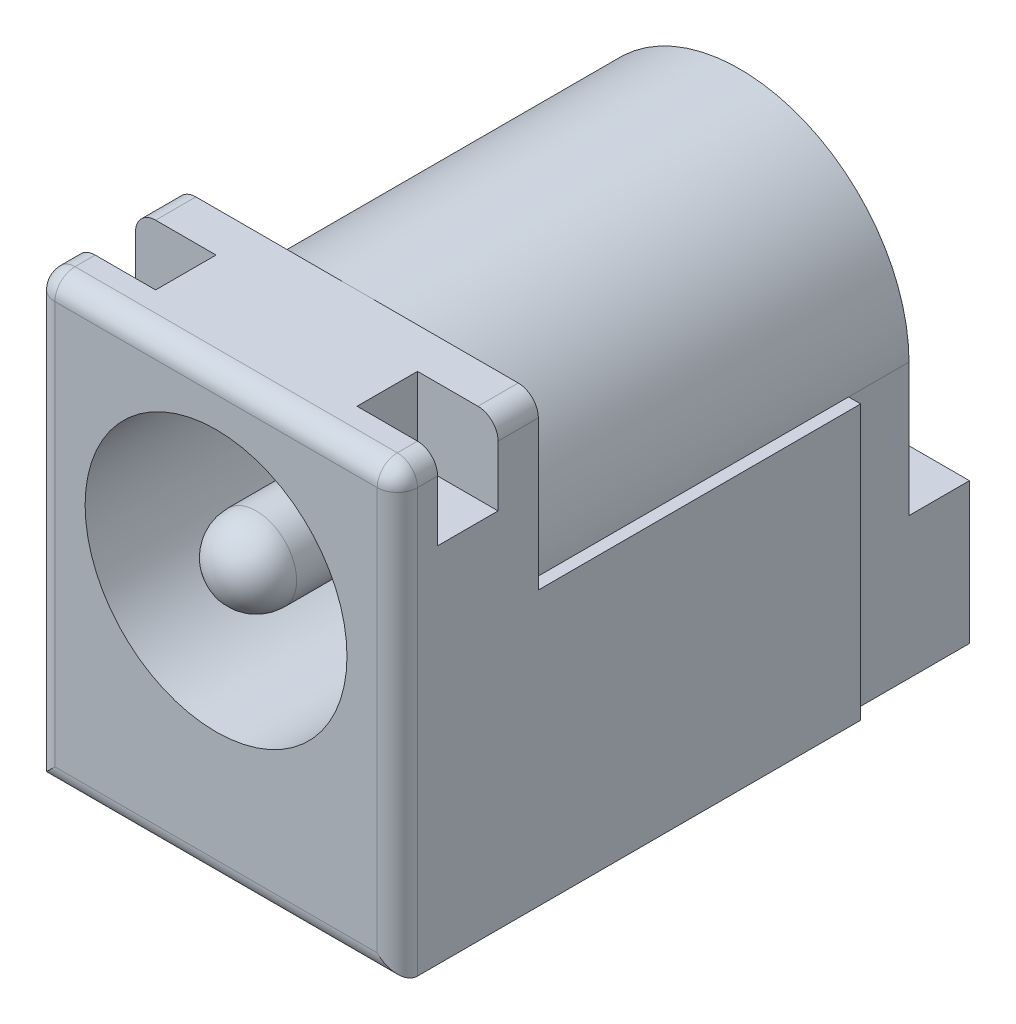
SolidWorks part; units mm, degrees
ref_plane "Front Plane" through (0, 0, 0) normal (0, 0, 1) x (1, 0, 0)
ref_plane "Top Plane" through (0, 0, 0) normal (0, 1, 0) x (1, 0, 0)
ref_plane "Right Plane" through (0, 0, 0) normal (1, 0, 0) x (0, 0, -1)
sketch "Sketch1" plane through (0, 0, 0) normal (0, 0, 1) x (1, 0, 0)
  line L1 (-4.5, 5.5) -> (4.5, 5.5)
  line L2 (-4.5, 5.5) -> (-4.5, -5.5)
  line L3 (-4.5, -5.5) -> (4.5, -5.5)
  line L4 (4.5, 5.5) -> (4.5, -5.5)
  line L5 (-4.5, 5.5) -> (4.5, -5.5) construction
  line L6 (-4.5, -5.5) -> (4.5, 5.5) construction
  point P0 (0, 0)
  dimension "D1" = 9
  dimension "D2" = 11
extrude "Boss-Extrude1" add sketch "Sketch1" against normal blind 14.5
sketch "Sketch2" plane through (0, 0, -14.5) normal (0, 0, -1) x (-1, 0, 0)
  line L0 (-4.2, 1.3) -> (4.2, 1.3)
  line L4 (4.5, 5.5) -> (4.5, -5.5) construction
  line L5 (-4.5, 5.5) -> (4.5, 5.5) construction
  line L6 (-4.2, 1.3) -> (-4.5, 1.3)
  line L7 (-4.5, -5.5) -> (-4.5, 5.5) construction
  line L8 (4.2, 1.3) -> (4.5, 1.3)
  arc A0 (-4.2, 1.3) -> (4.2, 1.3) centre (0, 1.3) cw
  line M3 (-4.5, 5.5) -> (-4.5, -5.5)
  line M5 (4.5, -5.5) -> (4.5, 5.5)
  line M6 (4.5, 5.5) -> (-4.5, 5.5)
  dimension "D2" = 0.3
extrude "Cut-Extrude3" cut sketch "Sketch2" against normal blind 11 contours L6 A0 M6 M3 | A0 L8 M6 M5
sketch "Sketch3" plane through (4.5, 0, 0) normal (1, 0, 0) x (0, 0, -1)
  line L0 (14.5, -5.5) -> (14.5, 1.3)
  line L1 (14.5, -5.5) -> (14.5, 1.3) construction
  line L4 (3.5, 1.3) -> (14.5, 1.3) construction
  line L5 (14.5, 1.3) -> (11.5, 1.3)
  line L6 (11.5, 1.3) -> (11.5, -5.5)
  line L7 (14.5, -5.5) -> (0, -5.5) construction
  line L8 (11.5, -5.5) -> (14.5, -5.5)
  dimension "D1" = 3
extrude "Cut-Extrude4" cut sketch "Sketch3" against normal blind 0.3
mirror "Mirror1" about plane through (0, 0, 0) normal (1, 0, 0) of "Cut-Extrude4"
sketch "Sketch5" plane through (4.2, 0, 0) normal (1, 0, 0) x (0, 0, -1)
  line L0 (14.5, -5.5) -> (14.5, 1.3) construction
  line L1 (14.5, -2) -> (13, -2)
  line L2 (14.5, -2) -> (14.5, 5.5)
  line L3 (14.5, 5.5) -> (13, 5.5)
  line L4 (13, -2) -> (13, 5.5)
  line L5 (14.5, 5.5) -> (3.5, 5.5) construction
  line L6 (11.5, 1.3) -> (11.5, -5.5) construction
  line L7 (11.5, -5.5) -> (14.5, -5.5) construction
  dimension "D1" = 1.5
  dimension "D2" = 3.5
extrude "Cut-Extrude5" cut sketch "Sketch5" against normal through all
sketch "Sketch6" plane through (0, 0, -14.5) normal (0, 0, -1) x (-1, 0, 0)
  line L0 (4.2, -5.5) -> (-4.2, -5.5) construction
  line L1 (-1.75, -5.5) -> (1.75, -5.5)
  line L2 (-1.75, -5.5) -> (-1.75, -2)
  line L3 (-1.75, -2) -> (1.75, -2)
  line L4 (1.75, -5.5) -> (1.75, -2)
  line L5 (4.2, -2) -> (-4.2, -2) construction
  point P8 (0, -5.5)
  point P9 (0, -2)
  dimension "D1" = 3.5
extrude "Cut-Extrude6" cut sketch "Sketch6" against normal up to surface (1.5 mm away) up to face at (0, 0.7, -13)
sketch "Sketch7" plane through (0, 0, -13) normal (0, 0, -1) x (-1, 0, 0)
  line L0 (0, 1.3) -> (0, -7.5) construction
  line L1 (1.5, 1.3) -> (1.5, -7.5)
  line L2 (-1.5, 1.3) -> (-1.5, -7.5)
  line L4 (-4.5891, -9) -> (7.0324, -9) construction
  line L5 (4.2, -5.5) -> (1.75, -5.5) construction
  line L6 (-1.5, 1.3) -> (1.5, 1.3) construction
  line L7 (4.2, 1.3) -> (4.5, 1.3) construction
  arc A0 (1.5, 1.3) -> (-1.5, 1.3) centre (0, 1.3) ccw
  arc A1 (-1.5, -7.5) -> (1.5, -7.5) centre (0, -7.5) ccw
  point P2 (0, -3.1)
  dimension "D2" = 3.5
  dimension "D1" = 3
extrude "Boss-Extrude2" add sketch "Sketch7" along normal blind 0.5
sketch "Sketch8" plane through (0, 0, -13.5) normal (0, 0, -1) x (-1, 0, 0)
  circle A0 centre (0, 1.3) radius 1.375
  circle A2 centre (0, 1.3) radius 1
  dimension "D1" = 2.75
  dimension "D2" = 2
extrude "Boss-Extrude3" add sketch "Sketch8" along normal blind 0.5 contours A0 A2
chamfer "Chamfer1" distance 0.5 angle 45 1 edges at (-1.375, 1.3, -14)
sketch "Sketch9" plane through (0, -5.5, 0) normal (0, -1, 0) x (1, 0, 0)
  line L0 (0, 0) -> (0, -13) construction
  line L1 (-1.25, -7) -> (1.25, -7)
  line L2 (-1.25, -7) -> (-1.25, -7.5)
  line L3 (-1.25, -7.5) -> (1.25, -7.5)
  line L4 (1.25, -7) -> (1.25, -7.5)
  line L5 (1.5, -13) -> (-1.5, -13) construction
  line L6 (-1.25, -7.5) -> (1.25, -7) construction
  point P9 (0, -7.25)
  point P10 (0, -7)
  dimension "D1" = 0.5
  dimension "D2" = 2.5
  dimension "D3" = 5.75
extrude "Boss-Extrude4" add sketch "Sketch9" along normal blind 6
sketch "Sketch10" plane through (0, 0, -7) normal (0, 0, 1) x (1, 0, 0)
  line L0 (-1.25, -11.5) -> (-1.25, -5.5) construction
  line L1 (1.25, -11.5) -> (1.25, -5.5) construction
  line L2 (-1.0662, -9) -> (1.0355, -9) construction
  line L3 (-4.5, -5.5) -> (4.5, -5.5) construction
  line L4 (-1.25, -8.3292) -> (1.25, -8.3292)
  arc A1 (-1.25, -8.3292) -> (1.25, -8.3292) centre (0, -7.5) ccw
  dimension "D1" = 1.5
  dimension "D2" = 3.5
extrude "Cut-Extrude8" cut sketch "Sketch10" against normal blind 0.5
sketch "Sketch11" plane through (0, 0, -13.5) normal (0, 0, -1) x (-1, 0, 0)
  circle A0 centre (0, -7.5) radius 0.6
  dimension "D1" = 1.2
extrude "Cut-Extrude9" cut sketch "Sketch11" against normal through all
sketch "Sketch12" plane through (4.5, 0, 0) normal (1, 0, 0) x (0, 0, -1)
  line L0 (3.5, 5.5) -> (0, 5.5) construction
  line L1 (1, 5.5) -> (2.5, 5.5)
  line L2 (1, 5.5) -> (1, 3.5)
  line L3 (1, 3.5) -> (2.5, 3.5)
  line L4 (2.5, 5.5) -> (2.5, 3.5)
  line L5 (1, 4.7806) -> (0, 4.7806) construction
  line L6 (0, -5.5) -> (0, 5.5) construction
  line L7 (2.5, 4.7806) -> (3.5, 4.7806) construction
  line L8 (3.5, 5.5) -> (3.5, 1.3) construction
  dimension "D1" = 1.5
  dimension "D2" = 2
extrude "Cut-Extrude10" cut sketch "Sketch12" against normal blind 2
mirror "Mirror2" about plane through (0, 0, 0) normal (1, 0, 0) of "Cut-Extrude10"
sketch "Sketch13" plane through (0, 0, 0) normal (0, 0, 1) x (1, 0, 0)
  line L0 (-4.5, -5.5) -> (4.5, -5.5) construction
  circle A0 centre (0, 1) radius 3.25
  circle A1 centre (0, 1) radius 1
  dimension "D1" = 6.5
  dimension "D2" = 6.5
  dimension "D3" = 2
extrude "Cut-Extrude11" cut sketch "Sketch13" against normal blind 12 contours A0 A1
fillet "Fillet1" radius 1 1 edges at (1, 1, 0)
fillet "Fillet2" radius 0.5 8 edges at (-4.5, 5.5, -0.5) (-4.5, 5.5, -3) (4.5, 5.5, -0.5) (4.5, 5.5, -3) (0, -5.5, 0) (0, 5.5, 0) (-4.5, 0, 0) (4.5, 0, 0)
sketch "Sketch14" plane through (0, 0, -14.5) normal (0, 0, -1) x (-1, 0, 0)
  point P0 (-3.0976, -3.9034)
  point P1 (3.0976, -3.8186)
ref_plane "Plane1" through (0, 0, -19.5) normal (0, 0, -1) x (-1, 0, 0)
sketch "Sketch15" plane through (0, 0, -19.5) normal (0, 0, -1) x (-1, 0, 0)
  point P0 (-3.0976, -3.9034)
  point P1 (3.0976, -3.8186)
